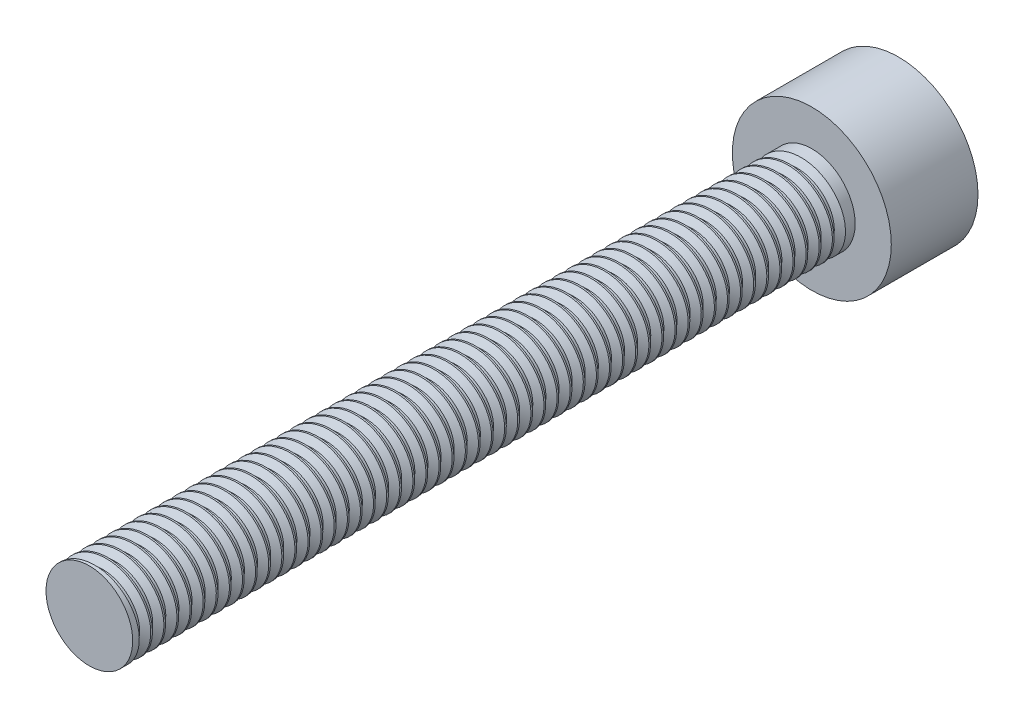
SolidWorks part; units mm, degrees
ref_plane "前视基准面" through (0, 0, 0) normal (0, 0, 1) x (1, 0, 0)
ref_plane "上视基准面" through (0, 0, 0) normal (0, 1, 0) x (1, 0, 0)
ref_plane "右视基准面" through (0, 0, 0) normal (1, 0, 0) x (0, 0, -1)
sketch "草图1" plane through (0, 0, 0) normal (0, 0, 1) x (1, 0, 0)
  circle A0 centre (0, 0) radius 2.75
  dimension "D1" = 5.5
extrude "凸台-拉伸1" add sketch "草图1" along normal blind 3
sketch "草图2" plane through (0, 0, 3) normal (0, 0, 1) x (1, 0, 0)
  circle A0 centre (0, 0) radius 1.5
  dimension "D1" = 3
extrude "凸台-拉伸2" add sketch "草图2" along normal blind 25
sketch "草图3" plane through (0, 0, 0) normal (0, 0, -1) x (-1, 0, 0)
  line L1 (1.1762, -1.2714) -> (1.6892, 0.3829)
  line L2 (1.6892, 0.3829) -> (0.513, 1.6543)
  line L3 (0.513, 1.6543) -> (-1.1762, 1.2714)
  line L4 (-1.1762, 1.2714) -> (-1.6892, -0.3829)
  line L5 (-1.6892, -0.3829) -> (-0.513, -1.6543)
  line L6 (-0.513, -1.6543) -> (1.1762, -1.2714)
  circle A0 centre (0, 0) radius 1.5 construction
  dimension "D1" = 3
extrude "切除-拉伸1" cut sketch "草图3" against normal blind 1.5
thread "螺纹线1" pitch 0.4536 method cut profile "螺纹线轮廓1" start angle 0, offset 0, length 24.5, pitch 0.4536, diameter 3
ref_plane "基准面4" through (-1.5, 0, 28) normal (0, -1, 0) x (-1, 0, 0)
sketch "螺纹线轮廓1" plane through (-1.5, 0, 28) normal (0, -1, 0) x (-1, 0, 0)
  line L0 (0, 0) -> (0, 0.4536) construction
  line L11 (0, 0) -> (0, 0.3969)
  line L12 (0, 0.3969) -> (-0.2455, 0.2551)
  line L13 (-0.2455, 0.2551) -> (-0.2455, 0.1417)
  line L15 (-0.2455, 0.1417) -> (0, 0)
  line L17 (-0.2455, 0.1984) -> (0, 0.1984) construction
  point P2 (0, 0)
  dimension "Pitch" = 0.4536
  dimension "Profile_Angle" = 60
  dimension "Profile_Land" = 0.1134
  dimension "Profile_Height" = 0.2455
